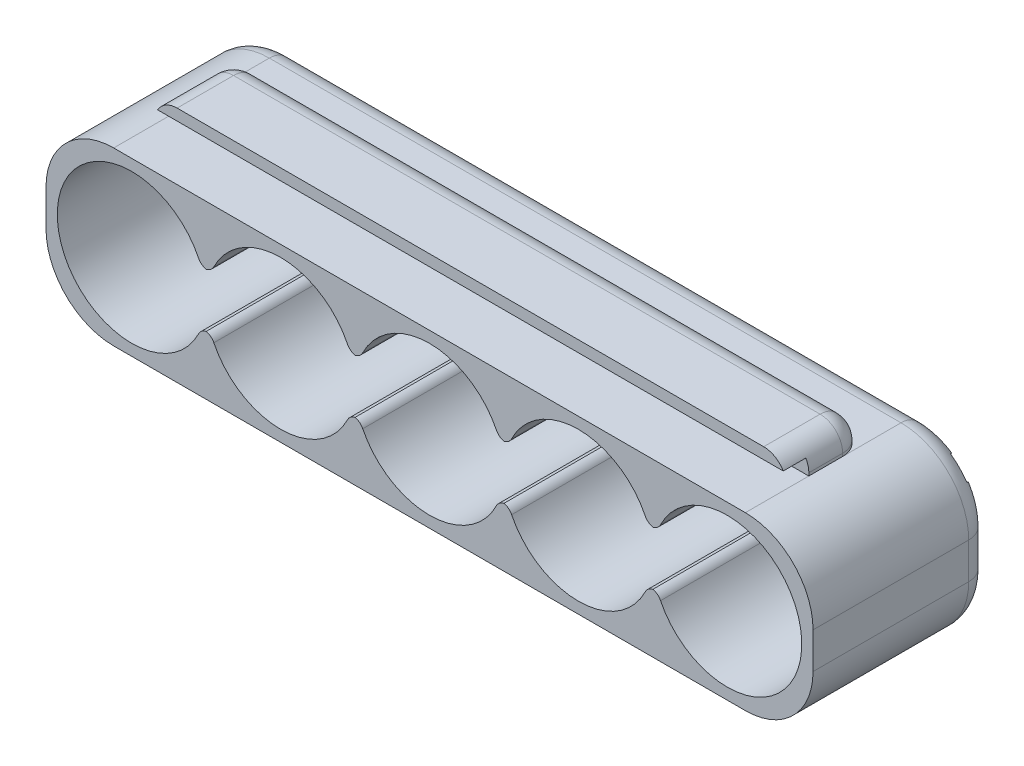
SolidWorks part; units mm, degrees
ref_plane "Front" through (0, 0, 0) normal (0, 0, 1) x (1, 0, 0)
ref_plane "Top" through (0, 0, 0) normal (0, 1, 0) x (1, 0, 0)
ref_plane "Right" through (0, 0, 0) normal (1, 0, 0) x (0, 0, -1)
sketch "Sketch1" plane through (0, 0, 0) normal (0, 0, 1) x (1, 0, 0)
  line L0 (0, 0) -> (13.2, 0) construction
  line L1 (0, -6.6) -> (52.8, -6.6) construction
  line L2 (39.6, 6.6) -> (39.6, -6.6) construction
  line L3 (-1.6, -7.6) -> (54.4, -7.6)
  line L4 (-7.6, -1.6) -> (-7.6, 1.6)
  line L5 (-1.6, 7.6) -> (54.4, 7.6)
  line L6 (60.4, -1.6) -> (60.4, 1.6)
  line L7 (-7.6, -7.6) -> (60.4, 7.6) construction
  line L8 (-7.6, 7.6) -> (60.4, -7.6) construction
  line L9 (-6.6, 0) -> (59.4, 0) construction
  line L10 (-6.6, 0) -> (-6.6, -7.6) construction
  line L11 (6.1636, 2.36) -> (7.0364, 2.36)
  line L12 (6.1636, -2.36) -> (7.0364, -2.36)
  line L13 (6.6, 7.6) -> (6.6, -7.6) construction
  line L14 (33.4364, -2.36) -> (32.5636, -2.36)
  line L15 (33.4364, 2.36) -> (32.5636, 2.36)
  line L16 (13.2, 7.6) -> (13.2, -6.6) construction
  line L17 (20.2364, -2.36) -> (19.3636, -2.36)
  line L18 (20.2364, 2.36) -> (19.3636, 2.36)
  line L19 (45.7636, -2.36) -> (46.6364, -2.36)
  line L20 (45.7636, 2.36) -> (46.6364, 2.36)
  arc A0 (6.1636, 2.36) -> (6.1636, -2.36) centre (0, 0) ccw
  arc A8 (54.4, 7.6) -> (60.4, 1.6) centre (54.4, 1.6) cw
  arc A9 (54.4, -7.6) -> (60.4, -1.6) centre (54.4, -1.6) ccw
  arc A10 (-1.6, -7.6) -> (-7.6, -1.6) centre (-1.6, -1.6) cw
  arc A11 (-7.6, 1.6) -> (-1.6, 7.6) centre (-1.6, 1.6) cw
  arc A12 (7.0364, -2.36) -> (19.3636, -2.36) centre (13.2, 0) ccw
  arc A13 (32.5636, 2.36) -> (20.2364, 2.36) centre (26.4, 0) ccw
  arc A14 (33.4364, -2.36) -> (45.7636, -2.36) centre (39.6, 0) ccw
  arc A15 (20.2364, -2.36) -> (32.5636, -2.36) centre (26.4, 0) ccw
  arc A16 (19.3636, 2.36) -> (7.0364, 2.36) centre (13.2, 0) ccw
  arc A17 (46.6364, -2.36) -> (46.6364, 2.36) centre (52.8, 0) ccw
  arc A18 (45.7636, 2.36) -> (33.4364, 2.36) centre (39.6, 0) ccw
  point P1 (26.4, 0)
  point P40 (6.6, 2.36)
  point P41 (6.6, -2.36)
  dimension "D1" = 13.2
  dimension "D4" = 6
  dimension "D3" = 1
  dimension "D2" = 1
  dimension "D5" = 15.2
  dimension "D7" = 13.2
  dimension "D9" = 2.36
  dimension "D6" = 4
extrude "Boss-Extrude1" add sketch "Sketch1" along normal blind 20
sketch "Sketch2" plane through (0, 0, 0) normal (0, 0, -1) x (-1, 0, 0)
  line L0 (-39.6, 0) -> (-26.6, 0) construction
  line L1 (-60.4, 0) -> (7.6, 0) construction
  line L2 (-39.6, 0) -> (-52.6, 0) construction
  line L4 (-60.4, 1.6) -> (-60.4, -1.6)
  line L5 (-54.4, -7.6) -> (1.6, -7.6)
  line L6 (7.6, -1.6) -> (7.6, 1.6)
  line L7 (1.6, 7.6) -> (-54.4, 7.6)
  line L8 (-60.4, 1.6) -> (-60.4, -1.6)
  line L9 (-54.4, -7.6) -> (1.6, -7.6)
  line L10 (7.6, -1.6) -> (7.6, 1.6)
  line L11 (1.6, 7.6) -> (-54.4, 7.6)
  circle A0 centre (-39.6, 0) radius 4
  circle A1 centre (-52.6, 0) radius 4
  circle A2 centre (-26.6, 0) radius 4
  circle A3 centre (-13.6, 0) radius 4
  arc A4 (-54.4, 7.6) -> (-60.4, 1.6) centre (-54.4, 1.6) ccw
  arc A5 (-60.4, -1.6) -> (-54.4, -7.6) centre (-54.4, -1.6) ccw
  arc A6 (1.6, -7.6) -> (7.6, -1.6) centre (1.6, -1.6) ccw
  arc A7 (7.6, 1.6) -> (1.6, 7.6) centre (1.6, 1.6) ccw
  arc A8 (-54.4, 7.6) -> (-60.4, 1.6) centre (-54.4, 1.6) ccw
  arc A9 (-60.4, -1.6) -> (-54.4, -7.6) centre (-54.4, -1.6) ccw
  arc A10 (1.6, -7.6) -> (7.6, -1.6) centre (1.6, -1.6) ccw
  arc A11 (7.6, 1.6) -> (1.6, 7.6) centre (1.6, 1.6) ccw
  circle A12 centre (-0.6, 0) radius 4
  circle A13 centre (-0.6, 0) radius 4
  circle A14 centre (-13.6, 0) radius 4
  circle A15 centre (-26.6, 0) radius 4
  circle A16 centre (-39.6, 0) radius 4
  arc A17 (-45.7636, -2.36) -> (-33.4364, -2.36) centre (-39.6, 0) ccw construction
  arc M10 (-54.4, 7.6) -> (-60.4, 1.6) centre (-54.4, 1.6) ccw
  line M11 (-60.4, 1.6) -> (-60.4, -1.6)
  arc M12 (-60.4, -1.6) -> (-54.4, -7.6) centre (-54.4, -1.6) ccw
  line M13 (-54.4, -7.6) -> (1.6, -7.6)
  arc M14 (1.6, -7.6) -> (7.6, -1.6) centre (1.6, -1.6) ccw
  line M15 (7.6, -1.6) -> (7.6, 1.6)
  arc M16 (7.6, 1.6) -> (1.6, 7.6) centre (1.6, 1.6) ccw
  line M17 (1.6, 7.6) -> (-54.4, 7.6)
  arc M18 (-6.1636, 2.36) -> (-6.1636, -2.36) centre (0, 0) cw
  line M36 (-20.2364, 2.36) -> (-19.3636, 2.36)
  arc M37 (-19.3636, 2.36) -> (-7.0364, 2.36) centre (-13.2, 0) cw
  line M38 (-7.0364, 2.36) -> (-6.1636, 2.36)
  line M39 (-6.1636, -2.36) -> (-7.0364, -2.36)
  arc M40 (-7.0364, -2.36) -> (-19.3636, -2.36) centre (-13.2, 0) cw
  line M41 (-19.3636, -2.36) -> (-20.2364, -2.36)
  arc M42 (-20.2364, -2.36) -> (-32.5636, -2.36) centre (-26.4, 0) cw
  line M43 (-32.5636, -2.36) -> (-33.4364, -2.36)
  arc M44 (-33.4364, -2.36) -> (-45.7636, -2.36) centre (-39.6, 0) cw
  line M45 (-33.4364, 2.36) -> (-32.5636, 2.36)
  arc M46 (-32.5636, 2.36) -> (-20.2364, 2.36) centre (-26.4, 0) cw
  dimension "D2" = 8
  dimension "D4" = 13
  dimension "D6" = 13
  dimension "D1" = 0
  dimension "D3" = 4
  dimension "D5" = 2
extrude "Boss-Extrude2" add sketch "Sketch2" along normal blind 0.8 contours M17 M10 M11 M12 M13 M14 M15 M16 M46 M36 M37 M38 M18 M39 M40 M41 M42 M43 M44 M45 | A12 A3 A2 A0 M36 M46 M45 M44 M43 M42 M41 M40 M39 M18 M38 M37
fillet "Fillet1" radius 1 16 edges at (19.3636, 2.36, 10) (20.2364, 2.36, 10) (32.5636, 2.36, 10) (32.5636, -2.36, 10) (33.4364, -2.36, 10) (19.3636, -2.36, 10) (20.2364, -2.36, 10) (6.1636, -2.36, 10) (7.0364, -2.36, 10) (6.1636, 2.36, 10) (7.0364, 2.36, 10) (45.7636, -2.36, 10) (46.6364, -2.36, 10) (46.6364, 2.36, 10) (45.7636, 2.36, 10) (33.4364, 2.36, 10)
ref_plane "Plane1" through (54.4, 0, 0) normal (1, 0, 0) x (0, 0, -1)
sketch "Sketch4" plane through (54.4, 0, 0) normal (1, 0, 0) x (0, 0, -1)
  line L0 (-30.5, 7.6) -> (-9.5, 7.6) construction
  line L1 (-9.5, 7.6) -> (-9.5, 8.6) construction
  line L2 (-9.375, 7.6) -> (-9.375, 8.85)
  line L3 (-20, 7.6) -> (0.8, 7.6) construction
  line L4 (-9.375, 8.85) -> (-11.375, 8.85)
  line L5 (-11.375, 8.85) -> (-11.375, 9.85)
  line L6 (-11.375, 9.85) -> (-6.375, 9.85)
  line L7 (-4.375, 7.85) -> (-4.375, 7.6)
  line L8 (-9.5, 7.6) -> (-4.375, 7.6)
  line L9 (-20, 7.6) -> (0.8, 7.6) construction
  arc A0 (-6.375, 9.85) -> (-4.375, 7.85) centre (-6.375, 7.85) cw
  point P2 (-20, 7.6)
  dimension "D7" = 2
  dimension "D1" = 21
  dimension "D2" = 1
  dimension "D3" = 0.25
  dimension "D4" = 2
  dimension "D5" = 1
  dimension "D6" = 1.25
  dimension "D8" = 5
extrude "Boss-Extrude5" add sketch "Sketch4" against normal up to vertex (56 mm away) contours A0 L6 L5 L4 L2 L8 L7
fillet "Fillet3" radius 2 18 edges at (54.4, 9.2642, 4.9608) (54.4, 7.725, 4.375) (54.4, 8.85, 10.375) (54.4, 9.35, 11.375) (54.4, 9.85, 8.875) (-1.6, 9.2642, 4.9608) (-1.6, 7.725, 4.375) (-1.6, 8.85, 10.375) (-1.6, 9.35, 11.375) (-1.6, 9.85, 8.875) (26.4, 7.6, -0.8) (58.6426, 5.8426, -0.8) (60.4, 0, -0.8) (58.6426, -5.8426, -0.8) (26.4, -7.6, -0.8) (-5.8426, -5.8426, -0.8) (-7.6, 0, -0.8) (-5.8426, 5.8426, -0.8)
ref_plane "Plane2" through (0, 0, 15) normal (0, 0, 1) x (1, 0, 0)
other "SurfaceCut1"
sketch "Sketch5" plane through (0, 0, -0.8) normal (0, 0, -1) x (-1, 0, 0)
  line L0 (-26.4, 5.6) -> (-26.4, -5.6) construction
  line L1 (1.6, 5.6) -> (-54.4, 5.6) construction
  line L2 (-54.4, -5.6) -> (1.6, -5.6) construction
  line L4 (-52.8, -0.5) -> (0, -0.5)
  line L5 (-52.8, -0.5) -> (-52.8, 0.5)
  line L6 (-52.8, 0.5) -> (0, 0.5)
  line L7 (0, -0.5) -> (0, 0.5)
  line L8 (-52.8, -0.5) -> (0, 0.5) construction
  line L9 (-52.8, 0.5) -> (0, -0.5) construction
  point P6 (-26.4, 0)
  point P11 (0, 0)
  dimension "D1" = 1
extrude "Cut-Extrude1" cut sketch "Sketch5" against normal up to surface (0.8 mm away) up to face at (35.6, 0, 0)
sketch "Sketch6" plane through (0, 0, -0.8) normal (0, 0, -1) x (-1, 0, 0)
  line L0 (-26.4, 5.6) -> (-26.4, -5.6) construction
  line L1 (1.6, 5.6) -> (-54.4, 5.6) construction
  line L2 (-54.4, -5.6) -> (1.6, -5.6) construction
  line L3 (-52.6, 0) -> (-58.6738, 5.8113) construction
  line L4 (-51.8824, 0.75) -> (-53.3176, -0.75)
  line L5 (-51.8824, 0.75) -> (-57.9562, 6.5613)
  line L6 (-53.3176, -0.75) -> (-59.3913, 5.0613)
  line L7 (-57.9562, 6.5613) -> (-59.3913, 5.0613)
  line L8 (0.5176, -0.75) -> (6.5913, 5.0613)
  line L9 (5.1562, 6.5613) -> (6.5913, 5.0613)
  line L10 (-0.9176, 0.75) -> (5.1562, 6.5613)
  line L11 (-0.9176, 0.75) -> (0.5176, -0.75)
  arc A0 (-54.4, 5.6) -> (-58.4, 1.6) centre (-54.4, 1.6) ccw construction
  arc A1 (-54.4, 7.6) -> (-60.4, 1.6) centre (-54.4, 1.6) ccw construction
  point P12 (-57.2284, 4.4284)
  point P13 (-52.6, 0)
  point P19 (-58.6738, 5.8113)
  dimension "D1" = 1.5
extrude "Cut-Extrude2" cut sketch "Sketch6" against normal up to surface (0.8 mm away) up to face at (26.6, 0, 0)
fillet "Fillet4" radius 1 22 edges at (48.6314, -0.5, -0.4) (30.5686, -0.5, -0.4) (22.6314, -0.5, -0.4) (17.5686, -0.5, -0.4) (9.6314, -0.5, -0.4) (4.5686, -0.5, -0.4) (43.5686, -0.5, -0.4) (35.6314, -0.5, -0.4) (48.6314, 0.5, -0.4) (22.6314, 0.5, -0.4) (30.5686, 0.5, -0.4) (9.6314, 0.5, -0.4) (17.5686, 0.5, -0.4) (4.5686, 0.5, -0.4) (35.6314, 0.5, -0.4) (43.5686, 0.5, -0.4) (54.6736, 3.4206, -0.4) (56.1088, 1.9206, -0.4) (57.4709, 4.6629, 0) (-1.7109, 3.2649, -0.4) (-3.0384, 1.6619, -0.4) (-4.6709, 4.6629, 0)
